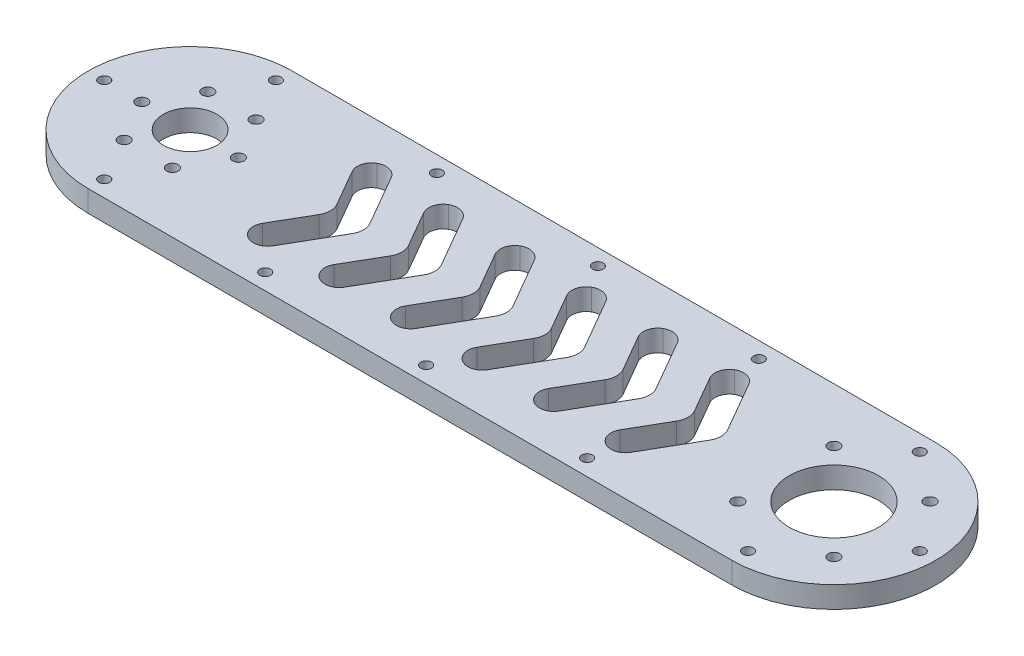
SolidWorks part; units mm, degrees
material "AISI 304"
ref_plane "前视基准面" through (0, 0, 0) normal (0, 0, 1) x (1, 0, 0)
ref_plane "上视基准面" through (0, 0, 0) normal (0, 1, 0) x (1, 0, 0)
ref_plane "右视基准面" through (0, 0, 0) normal (1, 0, 0) x (0, 0, -1)
sketch "草图1" plane through (0, 0, 0) normal (0, 1, 0) x (1, 0, 0)
  line L0 (0, 28.5) -> (180, 28.5)
  line L1 (0, -28.5) -> (180, -28.5)
  circle A0 centre (0, 0) radius 28.5
  circle A1 centre (180, 0) radius 28.5
  dimension "D1" = 57
  dimension "D2" = 57
  dimension "D3" = 180
extrude "凸台-拉伸1" add sketch "草图1" along normal blind 6 contours A0 | A1 L0 A0 L1 | A1 region at (90, 0, 0) region at (0, 0, 0) region at (180, 0, 0)
sketch "草图3" plane through (0, 6, 0) normal (0, 1, 0) x (1, 0, 0)
  circle A0 centre (0, 0) radius 13.5
  circle A1 centre (-13.5, 0) radius 1.6
  circle A2 centre (-6.75, 11.6913) radius 1.6
  circle A3 centre (6.75, 11.6913) radius 1.6
  circle A4 centre (13.5, 0) radius 1.6
  circle A5 centre (6.75, -11.6913) radius 1.6
  circle A6 centre (-6.75, -11.6913) radius 1.6
  point P18 (0, 0)
  dimension "D1" = 27
  dimension "D2" = 3.2
  dimension "D3" = 6
extrude "切除-拉伸1" cut sketch "草图3" against normal blind 16 contours A0 A1 | A0 A1 | A0 A2 | A0 A2 | A0 A3 | A0 A3 | A0 A4 | A0 A4 | A0 A5 | A0 A5 | A0 A6 | A0 A6 region at (12.8041, 6, 0) region at (14.1617, 6, 0) region at (6.4021, 6, -11.0887) region at (7.0808, 6, -12.2644) region at (7.0808, 6, 12.2644) region at (6.4021, 6, 11.0887) region at (-6.4021, 6, -11.0887) region at (-7.0808, 6, -12.2644) region at (-7.0808, 6, 12.2644) region at (-6.4021, 6, 11.0887) region at (-12.8041, 6, 0) region at (-14.1617, 6, 0)
sketch "草图4" plane through (0, 6, 0) normal (0, 1, 0) x (1, 0, 0)
  line L0 (180, 0) -> (193.435, 13.435) construction
  line L1 (280, 0) -> (299, 0) construction
  circle A0 centre (180, 0) radius 19
  circle A1 centre (193.435, 13.435) radius 1.6
  circle A2 centre (193.435, -13.435) radius 1.6
  circle A3 centre (180, 0) radius 19
  circle A4 centre (166.565, -13.435) radius 1.6
  circle A5 centre (180, 0) radius 19
  circle A6 centre (166.565, 13.435) radius 1.6
  circle A7 centre (180, 0) radius 19
  point P19 (180, 0)
  dimension "D1" = 38
  dimension "D2" = 3.2
  dimension "D3" = 45
  dimension "D4" = 4
extrude "切除-拉伸2" cut sketch "草图4" against normal blind 16 contours A5 A6 | A5 A6 | A3 A4 | A3 A4 | A0 A2 | A0 A2 | A0 A1 | A0 A1 region at (192.9464, 6, -12.9464) region at (193.9065, 6, -13.9065) region at (193.9065, 6, 13.9065) region at (192.9464, 6, 12.9464) region at (167.0536, 6, -12.9464) region at (166.0935, 6, -13.9065) region at (166.0935, 6, 13.9065) region at (167.0536, 6, 12.9464)
sketch "草图5" plane through (0, 6, 0) normal (0, 1, 0) x (1, 0, 0)
  line L0 (-44.2178, 0) -> (254.4494, 0) construction
  line L1 (40, 0) -> (30.7624, 16)
  line L2 (49.2376, 0) -> (37.6906, 20)
  line L3 (30.7624, 16) -> (37.6906, 20)
  line L4 (40, 0) -> (30.7624, -16)
  line L5 (49.2376, 0) -> (37.6906, -20)
  line L6 (30.7624, -16) -> (37.6906, -20)
  line L7 (60, 0) -> (50.7624, -16)
  line L8 (50.7624, -16) -> (57.6906, -20)
  line L9 (69.2376, 0) -> (57.6906, -20)
  line L10 (69.2376, 0) -> (57.6906, 20)
  line L11 (50.7624, 16) -> (57.6906, 20)
  line L12 (60, 0) -> (50.7624, 16)
  line L13 (80, 0) -> (70.7624, -16)
  line L14 (70.7624, -16) -> (77.6906, -20)
  line L15 (89.2376, 0) -> (77.6906, -20)
  line L16 (89.2376, 0) -> (77.6906, 20)
  line L17 (70.7624, 16) -> (77.6906, 20)
  line L18 (80, 0) -> (70.7624, 16)
  line L19 (100, 0) -> (90.7624, -16)
  line L20 (90.7624, -16) -> (97.6906, -20)
  line L21 (109.2376, 0) -> (97.6906, -20)
  line L22 (109.2376, 0) -> (97.6906, 20)
  line L23 (90.7624, 16) -> (97.6906, 20)
  line L24 (100, 0) -> (90.7624, 16)
  line L25 (120, 0) -> (110.7624, -16)
  line L26 (110.7624, -16) -> (117.6906, -20)
  line L27 (129.2376, 0) -> (117.6906, -20)
  line L28 (129.2376, 0) -> (117.6906, 20)
  line L29 (110.7624, 16) -> (117.6906, 20)
  line L30 (120, 0) -> (110.7624, 16)
  line L43 (30.7624, 16) -> (30.7624, -16) construction
  line L50 (140, 0) -> (130.7624, -16)
  line L51 (130.7624, -16) -> (137.6906, -20)
  line L52 (149.2376, 0) -> (137.6906, -20)
  line L53 (149.2376, 0) -> (137.6906, 20)
  line L54 (130.7624, 16) -> (137.6906, 20)
  line L55 (140, 0) -> (130.7624, 16)
  dimension "D1" = 60
  dimension "D2" = 8
  dimension "D3" = 20
  dimension "D4" = 40
  dimension "D5" = 6
extrude "切除-拉伸3" cut sketch "草图5" against normal blind 10
fillet "圆角2" radius 5 12 edges at (129.2376, 3, 0) (109.2376, 3, 0) (89.2376, 3, 0) (120, 3, 0) (100, 3, 0) (80, 3, 0) (60, 3, 0) (69.2376, 3, 0) (49.2376, 3, 0) (40, 3, 0) (140, 3, 0) (149.2376, 3, 0)
fillet "圆角3" radius 4 24 edges at (117.6906, 3, -20) (97.6906, 3, -20) (77.6906, 3, -20) (57.6906, 3, -20) (110.7624, 3, -16) (90.7624, 3, -16) (70.7624, 3, -16) (50.7624, 3, -16) (110.7624, 3, 16) (90.7624, 3, 16) (70.7624, 3, 16) (50.7624, 3, 16) (117.6906, 3, 20) (97.6906, 3, 20) (77.6906, 3, 20) (57.6906, 3, 20) (37.6906, 3, 20) (30.7624, 3, 16) (30.7624, 3, -16) (37.6906, 3, -20) (137.6906, 3, 20) (130.7624, 3, 16) (137.6906, 3, -20) (130.7624, 3, -16)
sketch "草图6" plane through (0, 6, 0) normal (0, 1, 0) x (1, 0, 0)
  line L0 (0, -24) -> (180, -24) construction
  circle A0 centre (0, 0) radius 24 construction
  circle A1 centre (0, 24) radius 1.5
  circle A2 centre (-24, 0) radius 1.5
  circle A3 centre (0, -24) radius 1.5
  circle A4 centre (180, 0) radius 24 construction
  circle A5 centre (180, 24) radius 1.5
  circle A7 centre (204, 0) radius 1.5
  circle A8 centre (180, -24) radius 1.5
  circle A9 centre (45, -24) radius 1.5
  circle A10 centre (45, 24) radius 1.5
  circle A11 centre (90, -24) radius 1.5
  circle A12 centre (90, 24) radius 1.5
  circle A13 centre (135, -24) radius 1.5
  circle A14 centre (135, 24) radius 1.5
  dimension "D1" = 48
  dimension "D2" = 3
  dimension "D3" = 3
  dimension "D4" = 3
  dimension "D5" = 48
  dimension "D6" = 3
  dimension "D7" = 3
  dimension "D8" = 3
  dimension "D9" = 4
sketch "草图7" plane through (0, 6, 0) normal (0, 1, 0) x (1, 0, 0)
  circle A0 centre (0, 0) radius 7.5
  circle A1 centre (180, 0) radius 12.5
  dimension "D1" = 15
  dimension "D2" = 25
extrude "切除-拉伸5" cut sketch "草图7" against normal blind 10
sketch "草图10" plane through (0, 0, 0) normal (0, -1, 0) x (1, 0, 0)
  circle A0 centre (6.75, 11.6913) radius 3
  circle A1 centre (13.5, 0) radius 3
  circle A2 centre (6.75, -11.6913) radius 3
  circle A3 centre (-6.75, -11.6913) radius 3
  circle A4 centre (-13.5, 0) radius 3
  circle A5 centre (-6.75, 11.6913) radius 3
  circle A6 centre (166.565, 13.435) radius 3
  circle A7 centre (193.435, 13.435) radius 3
  circle A8 centre (193.435, -13.435) radius 3
  circle A9 centre (166.565, -13.435) radius 3
  dimension "D1" = 6
  dimension "D2" = 6
  dimension "D3" = 6
  dimension "D4" = 6
  dimension "D5" = 6
  dimension "D6" = 6
  dimension "D7" = 6
  dimension "D8" = 6
  dimension "D9" = 6
  dimension "D10" = 6
extrude "切除-拉伸7" [suppressed] cut sketch "草图10" against normal blind 3
extrude "切除-拉伸8" cut sketch "草图6" against normal blind 10
